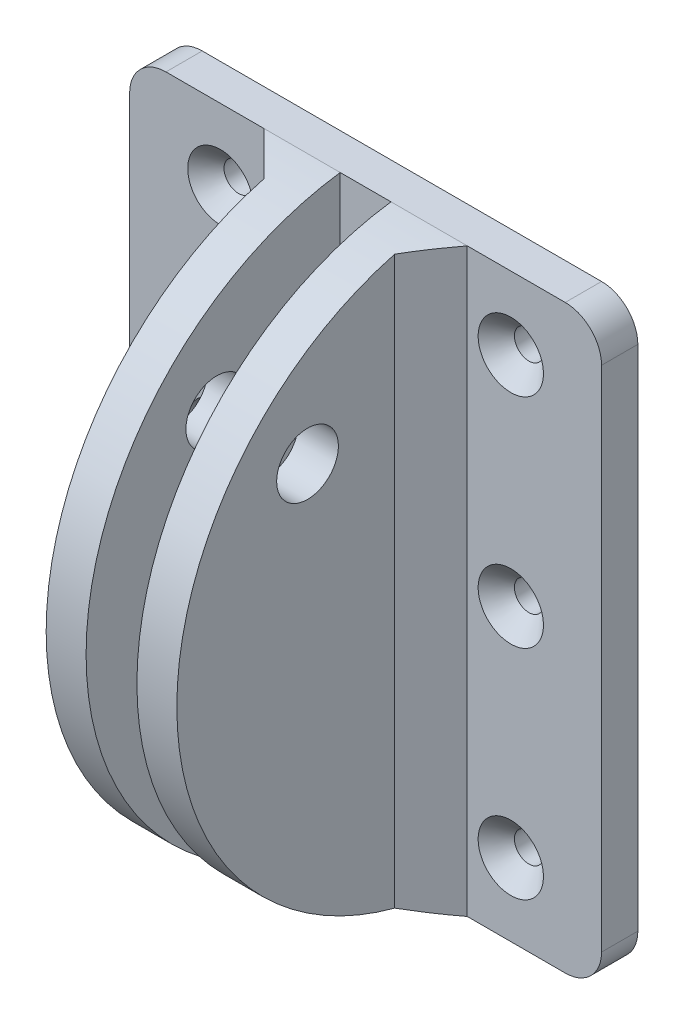
SolidWorks part; units mm, degrees
ref_plane "Front" through (0, 0, 0) normal (0, 0, 1) x (1, 0, 0)
ref_plane "Top" through (0, 0, 0) normal (0, 1, 0) x (1, 0, 0)
ref_plane "Right" through (0, 0, 0) normal (1, 0, 0) x (0, 0, -1)
sketch "Esquisse1" plane through (0, 0, 0) normal (0, 0, 1) x (1, 0, 0)
  line L1 (0, 0) -> (65, 0)
  line L2 (0, 0) -> (0, 80)
  line L3 (0, 80) -> (65, 80)
  line L4 (65, 0) -> (65, 80)
  dimension "D1" = 65
  dimension "D2" = 80
extrude "Boss.-Extru.1" add sketch "Esquisse1" along normal blind 5
sketch "Esquisse2" plane through (0, 0, 5) normal (0, 0, 1) x (1, 0, 0)
  line L0 (32.5, 0) -> (32.5, 80) construction
  line L1 (0, 0) -> (65, 0) construction
  line L2 (65, 80) -> (0, 80) construction
  line L3 (32.5, 40) -> (0, 40) construction
  line L4 (0, 80) -> (0, 0) construction
  line L5 (12.5, 40) -> (12.5, 70) construction
  line L6 (52.5, 40) -> (52.5, 70) construction
  circle A0 centre (12.5, 70) radius 2
  circle A1 centre (12.5, 10) radius 2
  circle A2 centre (12.5, 40) radius 2
  circle A3 centre (52.5, 40) radius 2
  circle A4 centre (52.5, 10) radius 2
  circle A5 centre (52.5, 70) radius 2
  dimension "D1" = 4
  dimension "D2" = 40
  dimension "D3" = 30
extrude "Enlèv. mat.-Extru.1" cut sketch "Esquisse2" against normal through all both and the other way through all
sketch "Esquisse3" plane through (0, 0, 5) normal (0, 0, 1) x (1, 0, 0)
  line L0 (32.5, 0) -> (32.5, 80) construction
  line L1 (0, 0) -> (65, 0) construction
  line L2 (65, 80) -> (0, 80) construction
  line L3 (41.5, 80) -> (23.5, 80)
  line L4 (23.5, 80) -> (23.5, 0)
  line L5 (23.5, 0) -> (41.5, 0)
  line L6 (41.5, 80) -> (41.5, 0)
  dimension "D1" = 18
extrude "Boss.-Extru.2" add sketch "Esquisse3" along normal blind 35
sketch "Esquisse4" plane through (23.5, 0, 0) normal (-1, 0, 0) x (0, 0, 1)
  line L0 (40, 80) -> (40, 0) construction
  line L1 (5, 80) -> (41, 80)
  line L2 (41, 80) -> (41, 0)
  line L3 (41, 0) -> (5, 0)
  arc A0 (5, 0) -> (5, 80) centre (-0.3571, 40) ccw
  point P7 (0, 0)
  point P12 (0, 0)
  point P13 (0, 0)
  point P14 (46.972, 0)
  dimension "D1" = 1
extrude "Enlèv. mat.-Extru.2" cut sketch "Esquisse4" against normal through all both and the other way through all
sketch "Esquisse5" plane through (23.5, 0, 0) normal (-1, 0, 0) x (0, 0, 1)
  line L0 (5, 80) -> (5, 0) construction
  line L1 (5, 80) -> (0, 80) construction
  circle A0 centre (22, 60) radius 4.25
  point P6 (2.5, 80)
  dimension "D1" = 8.5
  dimension "D2" = 17
  dimension "D3" = 20
extrude "Enlèv. mat.-Extru.3" cut sketch "Esquisse5" against normal through all both and the other way through all
sketch "Esquisse6" plane through (0, 0, 5) normal (0, 0, 1) x (1, 0, 0)
  line L0 (32.5, 0) -> (32.5, 80) construction
  line L1 (41.5, 0) -> (23.5, 0) construction
  line L2 (41.5, 80) -> (23.5, 80) construction
  line L3 (36, 80) -> (29, 80)
  line L4 (29, 80) -> (29, 0)
  line L5 (29, 0) -> (36, 0)
  line L6 (36, 80) -> (36, 0)
  dimension "D1" = 7
extrude "Enlèv. mat.-Extru.4" cut sketch "Esquisse6" along normal through all
chamfer "Chanfrein1" distance 5 angle 45 2 edges at (41.5, 40, 5) (23.5, 40, 5)
chamfer "Chanfrein2" distance 2.5 angle 45 6 edges at (50.5, 70, 5) (50.5, 40, 5) (50.5, 10, 5) (10.5, 10, 5) (10.5, 40, 5) (10.5, 70, 5)
fillet "Congé1" radius 5 4 edges at (0, 80, 2.5) (65, 80, 2.5) (65, 0, 2.5) (0, 0, 2.5)
